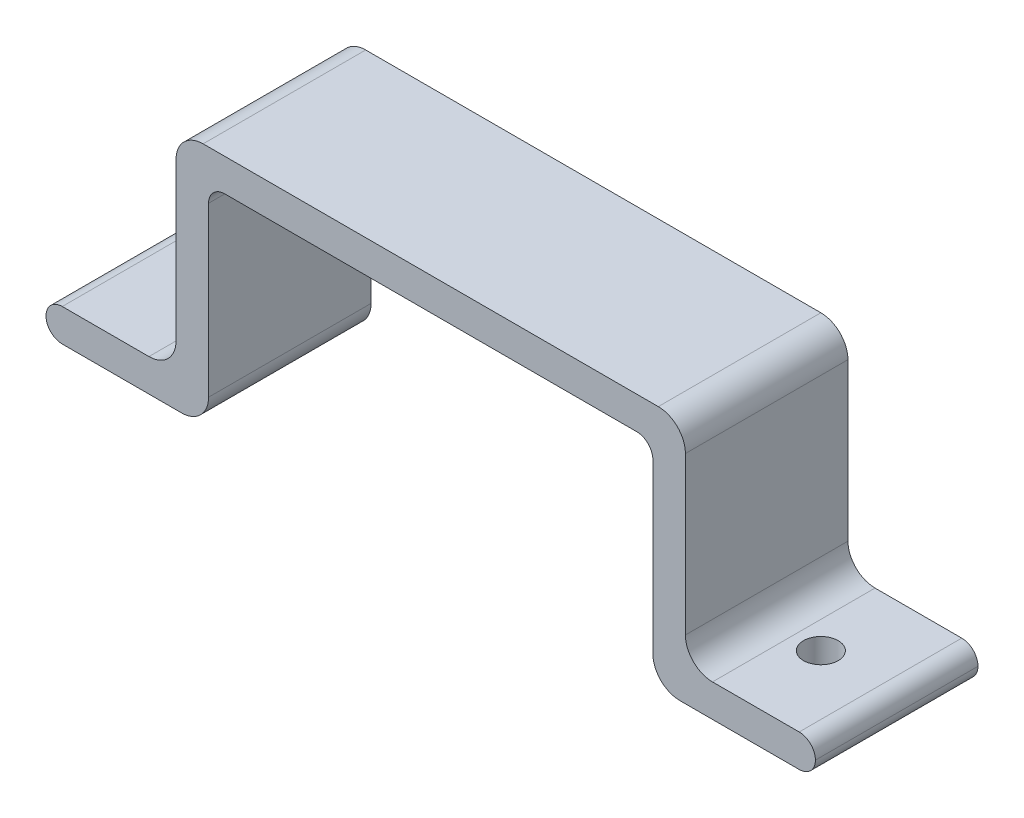
SolidWorks part; units mm, degrees
ref_plane "Front Plane" through (0, 0, 0) normal (0, 0, 1) x (1, 0, 0)
ref_plane "Top Plane" through (0, 0, 0) normal (0, 1, 0) x (1, 0, 0)
ref_plane "Right Plane" through (0, 0, 0) normal (1, 0, 0) x (0, 0, -1)
sketch "Sketch1" plane through (0, 0, 0) normal (0, 0, 1) x (1, 0, 0)
  line L0 (-23.5, 12.75) -> (23.5, 12.75)
  line L1 (23.5, 12.75) -> (23.5, -6.75)
  line L2 (23.5, -6.75) -> (35.5, -6.75)
  line L3 (35.5, -6.75) -> (35.5, -9.75)
  line L4 (35.5, -9.75) -> (20.5, -9.75)
  line L5 (20.5, -9.75) -> (20.5, 9.75)
  line L6 (20.5, 9.75) -> (-20.5, 9.75)
  line L7 (-20.5, 9.75) -> (-20.5, -9.75)
  line L8 (-20.5, -9.75) -> (-35.5, -9.75)
  line L9 (-35.5, -9.75) -> (-35.5, -6.75)
  line L10 (-35.5, -6.75) -> (-23.5, -6.75)
  line L11 (-23.5, -6.75) -> (-23.5, 12.75)
  line L12 (-23.5, 15.5222) -> (-20.5, 15.5222) construction
  line L13 (-10.112, 12.75) -> (-10.112, 9.75) construction
  line L14 (20.5, 12.1809) -> (23.5, 12.1809) construction
  point P3 (0, 12.75)
  point P22 (-20.5, 0)
  dimension "D1" = 41
  dimension "D2" = 3
  dimension "D3" = 19.5
  dimension "D4" = 15
extrude "Boss-Extrude1" add sketch "Sketch1" along normal mid plane 15
sketch "Sketch2" plane through (0, -6.75, 0) normal (0, 1, 0) x (1, 0, 0)
  line L0 (-35.5, -7.5) -> (-35.5, 7.5) construction
  line L1 (35.5, -7.5) -> (35.5, 7.5) construction
  line L2 (-35.5, 0) -> (-28.5, 0) construction
  line L3 (28.5, 0) -> (35.5, 0) construction
  circle A0 centre (-28.5, 0) radius 1.6
  circle A1 centre (28.5, 0) radius 1.6
  point P8 (-35.5, 0)
  point P12 (35.5, 0)
  dimension "D1" = 3.2
  dimension "D2" = 7
extrude "Cut-Extrude2" cut sketch "Sketch2" against normal through all
fillet "Fillet1" radius 2.5 6 edges at (-23.5, 12.75, 0) (23.5, 12.75, 0) (20.5, -9.75, 0) (23.5, -6.75, 0) (-20.5, -9.75, 0) (-23.5, -6.75, 0)
fillet "Fillet2" radius 1.5 6 edges at (35.5, -6.75, 0) (35.5, -9.75, 0) (20.5, 9.75, 0) (-20.5, 9.75, 0) (-35.5, -9.75, 0) (-35.5, -6.75, 0)
